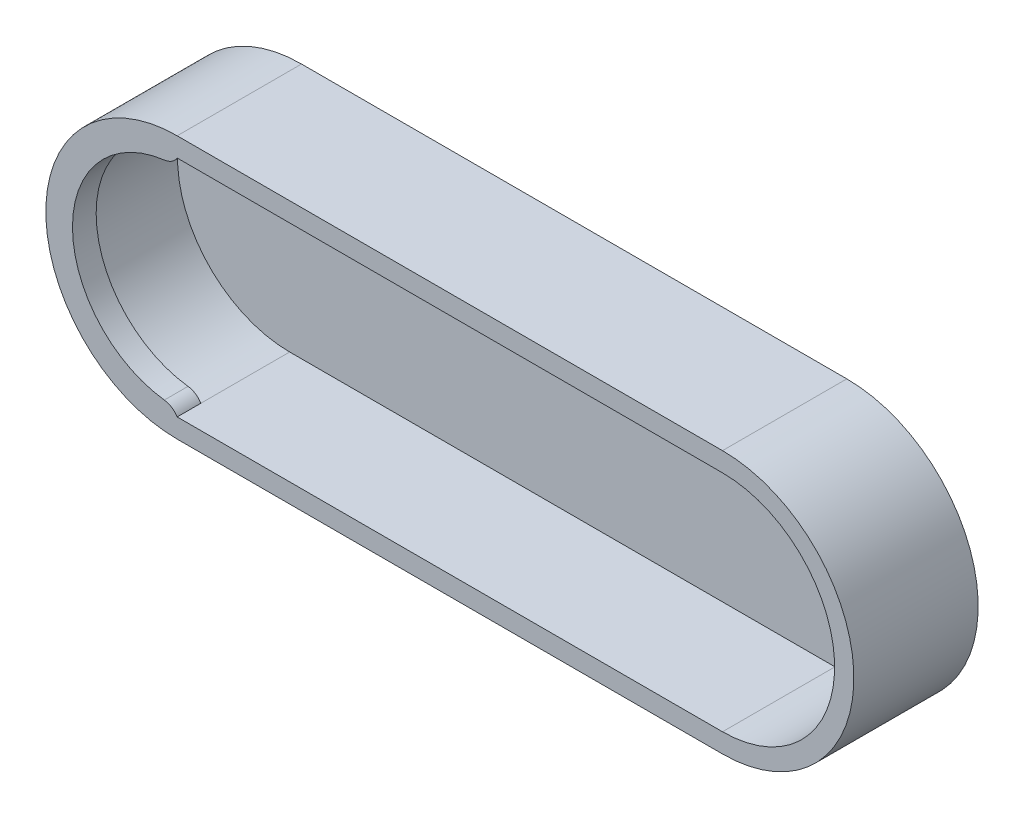
SolidWorks part; units mm, degrees
ref_plane "Front Plane" through (0, 0, 0) normal (0, 0, 1) x (1, 0, 0)
ref_plane "Top Plane" through (0, 0, 0) normal (0, 1, 0) x (1, 0, 0)
ref_plane "Right Plane" through (0, 0, 0) normal (1, 0, 0) x (0, 0, -1)
sketch "Sketch1" plane through (0, 0, 0) normal (0, 0, 1) x (1, 0, 0)
  line L1 (-46.06, 18.94) -> (46.06, 18.94)
  line L2 (-46.06, -18.94) -> (46.06, -18.94)
  line L3 (-46.06, 22.19) -> (46.06, 22.19)
  line L4 (-46.06, -22.19) -> (46.06, -22.19)
  arc A0 (-46.06, 18.94) -> (-46.06, -18.94) centre (-46.06, 0) ccw
  arc A1 (46.06, 18.94) -> (46.06, -18.94) centre (46.06, 0) cw
  arc A2 (46.06, 22.19) -> (46.06, -22.19) centre (46.06, 0) cw
  arc A3 (-46.06, 22.19) -> (-46.06, -22.19) centre (-46.06, 0) ccw
  point P4 (0, 0)
  point P7 (0, 18.94)
  point P8 (0, 0)
  point P11 (0, -18.94)
  point P13 (-65, 0)
  point P14 (65, 0)
  dimension "D2" = 130
  dimension "D3" = 3.25
extrude "Boss-Extrude3" add sketch "Sketch1" along normal blind 21
sketch "Sketch3" plane through (0, 0, 0) normal (0, 0, -1) x (-1, 0, 0)
  line L0 (-46.06, 18.94) -> (46.06, 18.94)
  line L1 (46.06, -18.94) -> (-46.06, -18.94)
  arc A0 (-46.06, 18.94) -> (-46.06, -18.94) centre (-46.06, 0) ccw
  arc A1 (46.06, 18.94) -> (46.06, -18.94) centre (46.06, 0) cw
extrude "Boss-Extrude4" add sketch "Sketch3" against normal blind 2 separate body
sketch "Sketch5" plane through (0, 0, 21) normal (0, 0, 1) x (1, 0, 0)
  line L1 (-46.06, 17.69) -> (-46.06, 18.94)
  line L2 (-46.06, -17.69) -> (-46.06, -18.94)
  arc A0 (-46.06, 18.94) -> (-46.06, -18.94) centre (-46.06, 0) ccw
  arc A1 (-46.06, 17.69) -> (-46.06, -17.69) centre (-46.06, 0) ccw
  point P0 (-46.06, 18.94)
  point P1 (-46.06, -18.94)
  point P7 (-64, 0)
  point P8 (-65, 0)
  point P9 (-46.06, 17.69)
  point P10 (-46.06, -17.69)
  dimension "D1" = 1
  dimension "D2" = 1.25
  dimension "D3" = 1.25
extrude "Boss-Extrude7" add sketch "Sketch5" against normal blind 4
fillet "Fillet3" radius 3 2 edges at (-46.06, 17.69, 19) (-46.06, -17.69, 19)
